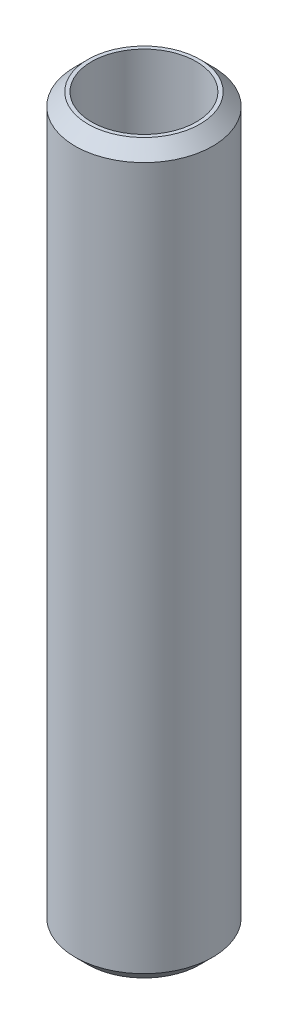
SolidWorks part; units mm, degrees
ref_plane "Front Plane" through (0, 0, 0) normal (0, 0, 1) x (1, 0, 0)
ref_plane "Top Plane" through (0, 0, 0) normal (0, 1, 0) x (1, 0, 0)
ref_plane "Right Plane" through (0, 0, 0) normal (1, 0, 0) x (0, 0, -1)
sketch "Sketch1" plane through (0, 0, 0) normal (0, 1, 0) x (1, 0, 0)
  circle A0 centre (0, 0) radius 20
  dimension "SHAFT_OD" = 40
extrude "Boss-Extrude1" add sketch "Sketch1" along normal blind 211.609
sketch "Sketch2" plane through (0, 0, 0) normal (0, 1, 0) x (1, 0, 0)
  circle A0 centre (0, 0) radius 15.2144
  dimension "BORE_D" = 30.4287
extrude "Cut-Extrude1" cut sketch "Sketch2" along normal through all
chamfer "Chamfer1" distance 3.7046 angle 45 2 edges at (0, 211.609, 20) (0, 0, 20)
